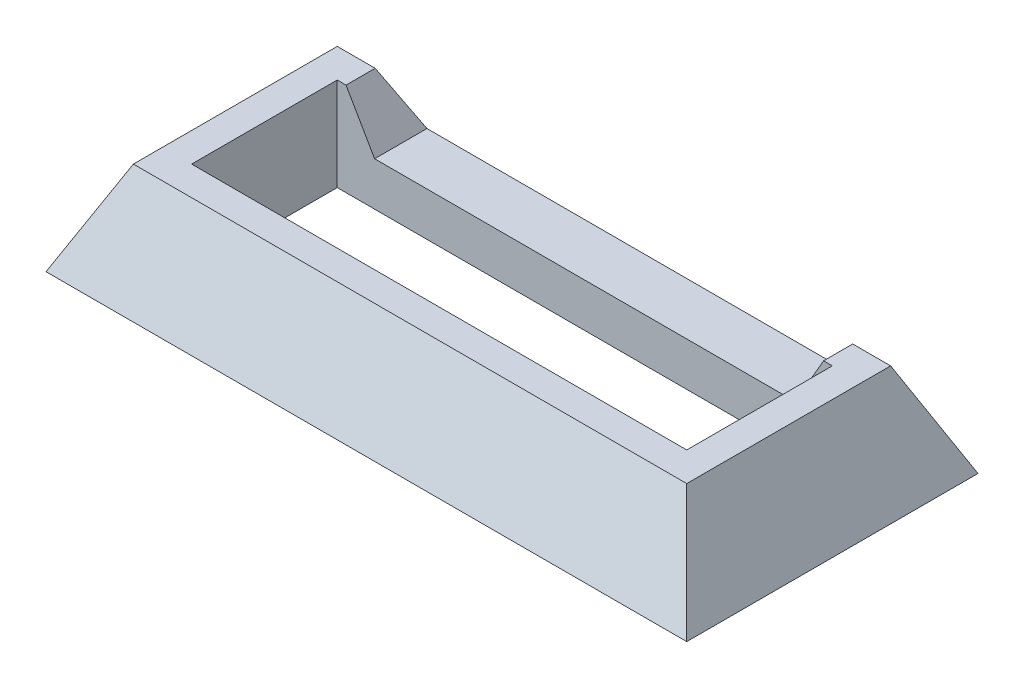
SolidWorks part; units mm, degrees
ref_plane "Alzado" through (0, 0, 0) normal (0, 0, 1) x (1, 0, 0)
ref_plane "Planta" through (0, 0, 0) normal (0, 1, 0) x (1, 0, 0)
ref_plane "Vista lateral" through (0, 0, 0) normal (1, 0, 0) x (0, 0, -1)
sketch "Croquis1" plane through (0, 0, 0) normal (0, 1, 0) x (1, 0, 0)
  line L1 (-8.5, 2.5) -> (8.5, 2.5)
  line L2 (-8.5, 2.5) -> (-8.5, -2.5)
  line L3 (-8.5, -2.5) -> (8.5, -2.5)
  line L4 (8.5, 2.5) -> (8.5, -2.5)
  line L5 (-8.5, 2.5) -> (8.5, -2.5) construction
  line L6 (-8.5, -2.5) -> (8.5, 2.5) construction
  line L7 (-11, 5) -> (11, 5)
  line L8 (-11, 5) -> (-11, -5)
  line L9 (-11, -5) -> (11, -5)
  line L10 (11, 5) -> (11, -5)
  line L11 (-11, 5) -> (11, -5) construction
  line L12 (-11, -5) -> (11, 5) construction
  point P0 (0, 0)
  point P6 (0, 0)
  dimension "D1" = 17
  dimension "D2" = 5
  dimension "D3" = 22
  dimension "D4" = 10
ref_plane "Plano1" through (0, 3.2, 0) normal (0, 1, 0) x (1, 0, 0)
sketch "Croquis2" plane through (0, 3.2, 0) normal (0, 1, 0) x (1, 0, 0)
  line L0 (-8.5, -2.5) -> (8.5, -2.5) construction
  line L1 (-8.5, 2.5) -> (-8.5, -2.5) construction
  line L2 (-8.5, 2.5) -> (8.5, 2.5) construction
  line L3 (8.5, 2.5) -> (8.5, -2.5) construction
  line L4 (-8.5, -2.5) -> (8.5, -2.5)
  line L5 (-8.5, 2.5) -> (-8.5, -2.5)
  line L6 (-8.5, 2.5) -> (8.5, 2.5)
  line L7 (8.5, 2.5) -> (8.5, -2.5)
  line L9 (-9.5, 3.5) -> (9.5, 3.5)
  line L10 (-9.5, 3.5) -> (-9.5, -3.5)
  line L11 (-9.5, -3.5) -> (9.5, -3.5)
  line L12 (9.5, 3.5) -> (9.5, -3.5)
  line L13 (-9.5, 3.5) -> (9.5, -3.5) construction
  line L14 (-9.5, -3.5) -> (9.5, 3.5) construction
  point P3 (0, 0)
  dimension "D1" = 19
  dimension "D2" = 7
loft "Recubrir1" add section "Croquis2" section "Croquis1" connector at (-9.5, 3.2, -3.5) connector at (-11, 0, -5)
extrude "Cortar-Extruir1" cut sketch "Croquis1<3>" along normal up to next contours L4 L1 L2 L3 region at (0, 0, 0)
sketch "Croquis1<3>" plane through (0, 0, 0) normal (0, 1, 0) x (1, 0, 0) same geometry as "Croquis1"
sketch "Croquis4" plane through (0, 0, 0) normal (0, 0, 1) x (1, 0, 0)
  line L0 (-11, 0) -> (11, 0) construction
  line L1 (7.2169, 1.5) -> (14.4338, 14)
  line L2 (14.4338, 14) -> (7.2169, 26.5)
  line L3 (7.2169, 26.5) -> (-7.2169, 26.5)
  line L4 (-7.2169, 26.5) -> (-14.4338, 14)
  line L5 (-14.4338, 14) -> (-7.2169, 1.5)
  line L6 (-7.2169, 1.5) -> (7.2169, 1.5)
  circle A0 centre (0, 14) radius 12.5 construction
  dimension "D1" = 25
  dimension "D2" = 14
extrude "Cortar-Extruir2" cut sketch "Croquis4" against normal up to next
